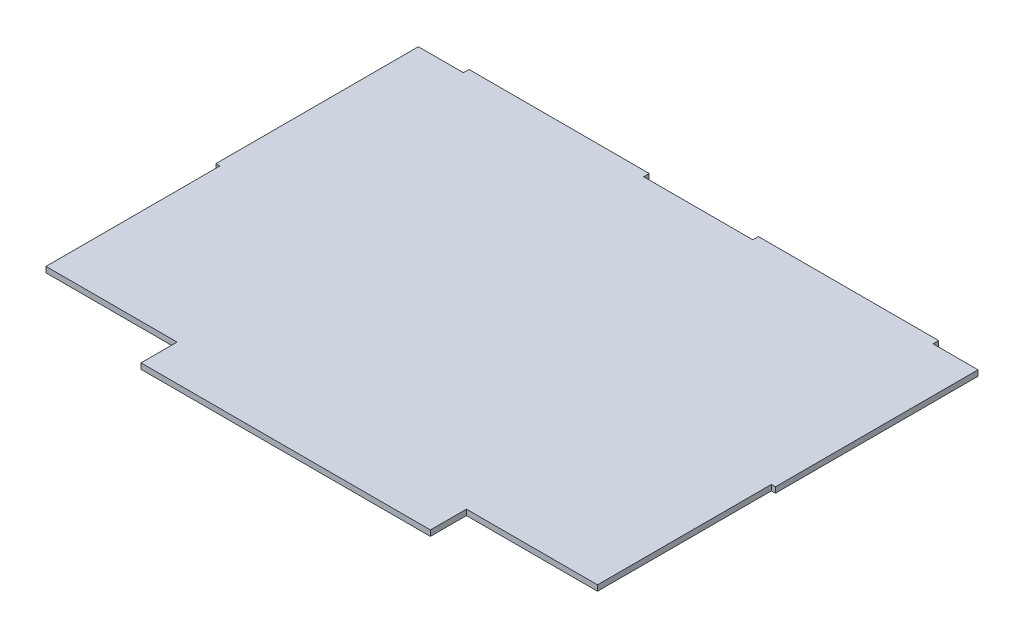
SolidWorks part; units mm, degrees
material "Custom Plastic"
ref_plane "X-Y Datum" through (0, 0, 0) normal (0, 0, 1) x (1, 0, 0)
ref_plane "X-Z Datum" through (0, 0, 0) normal (0, 1, 0) x (1, 0, 0)
ref_plane "Y-Z Datum" through (0, 0, 0) normal (1, 0, 0) x (0, 0, -1)
sketch "Sketch1" plane through (0, 0, 0) normal (0, 0, 1) x (1, 0, 0)
  line L1 (-157.7875, -1.5875) -> (157.7875, -1.5875)
  line L2 (-157.7875, -1.5875) -> (-157.7875, 1.5875)
  line L3 (-157.7875, 1.5875) -> (157.7875, 1.5875)
  line L4 (157.7875, -1.5875) -> (157.7875, 1.5875)
  line L5 (-157.7875, -1.5875) -> (157.7875, 1.5875) construction
  line L6 (-157.7875, 1.5875) -> (157.7875, -1.5875) construction
  point P0 (0, 0)
  dimension "D1" = 315.575
  dimension "D2" = 3.175
extrude "Boss-Extrude1" add sketch "Sketch1" along normal blind 235.775
sketch "Sketch3" plane through (0, 0, 0) normal (0, 0, -1) x (-1, 0, 0)
  line L0 (-157.7875, 0) -> (-81.5875, 0) construction
  line L1 (-157.7875, -1.5875) -> (-157.7875, 1.5875) construction
  line L2 (-157.7875, 1.5875) -> (157.7875, 1.5875) construction
  line L3 (-132.3875, -1.5875) -> (-30.7875, -1.5875)
  line L4 (-132.3875, -1.5875) -> (-132.3875, 1.5875)
  line L5 (-132.3875, 1.5875) -> (-30.7875, 1.5875)
  line L6 (-30.7875, -1.5875) -> (-30.7875, 1.5875)
  line L7 (-132.3875, -1.5875) -> (-30.7875, 1.5875) construction
  line L8 (-132.3875, 1.5875) -> (-30.7875, -1.5875) construction
  line L14 (-157.7875, 1.5875) -> (-132.3875, 1.5875)
  line L15 (-157.7875, 1.5875) -> (-157.7875, -1.5875)
  line L16 (-157.7875, -1.5875) -> (-132.3875, -1.5875)
  line L17 (-132.3875, 1.5875) -> (-132.3875, -1.5875)
  line L19 (-30.7875, 1.5875) -> (-30.7875, -1.5875)
  line L20 (0, 43.0151) -> (0, -43.0151) construction
  line L21 (30.7875, -1.5875) -> (30.7875, 1.5875)
  line L22 (132.3875, -1.5875) -> (132.3875, 1.5875)
  line L23 (132.3875, 1.5875) -> (30.7875, 1.5875)
  line L24 (132.3875, -1.5875) -> (30.7875, 1.5875) construction
  line L25 (132.3875, -1.5875) -> (30.7875, -1.5875)
  line L26 (132.3875, 1.5875) -> (30.7875, -1.5875) construction
  line M2 (-157.7875, 1.5875) -> (-157.7875, -1.5875)
  line M3 (-157.7875, -1.5875) -> (157.7875, -1.5875)
  line M4 (157.7875, -1.5875) -> (157.7875, 1.5875)
  line M5 (157.7875, 1.5875) -> (-157.7875, 1.5875)
  dimension "D1" = 76.2
  dimension "D2" = 101.6
extrude "Cut-Extrude1" cut sketch "Sketch3" against normal blind 3.175 contours L4 M3 M5 M2 | L6 M3 M5 | M3 M4 M5 region at (145.0875, 0, 0) region at (0, 0, 0) region at (-145.0875, 0, 0)
sketch "Sketch5" plane through (0, 1.5875, 0) normal (0, 1, 0) x (1, 0, 0)
  line L1 (-157.7875, -235.775) -> (-155.5015, -235.775)
  line L3 (-157.7875, -235.775) -> (-157.7875, -117.411)
  line L5 (-157.7875, -117.411) -> (-155.5015, -117.411)
  line L6 (-155.5015, -235.775) -> (-155.5015, -117.411)
  line M11 (-157.7875, -3.175) -> (-157.7875, -235.775)
  line M12 (-157.7875, -235.775) -> (157.7875, -235.775)
  dimension "D1" = 118.364
  dimension "D2" = 2.286
extrude "Cut-Extrude2" cut sketch "Sketch5" against normal blind 3.175 and the other way through all contours M12 M11 region at (-156.6445, 1.5875, 176.593)
mirror "Mirror1" about plane through (0, 0, 0) normal (1, 0, 0) of "Cut-Extrude2"
sketch "Sketch6" plane through (0, 1.5875, 0) normal (0, 1, 0) x (1, 0, 0)
  line L0 (-157.7925, -235.775) -> (-157.7925, -134.175) construction
  line L5 (155.5015, -235.775) -> (-155.5015, -235.775) construction
  line L8 (-157.7925, -235.775) -> (-73.389, -235.775)
  line L10 (-157.7925, -215.455) -> (-81.5925, -215.455)
  line L11 (-157.7925, -215.455) -> (-157.7925, -235.775)
  line L12 (-157.7925, -235.775) -> (-81.5925, -235.775)
  line L13 (-81.5925, -215.455) -> (-81.5925, -235.775)
  line M18 (-155.5015, -117.411) -> (-155.5015, -235.775)
  line M19 (-155.5015, -235.775) -> (155.5015, -235.775)
  dimension "D1" = 76.2
  dimension "D2" = 20.32
extrude "Cut-Extrude4" cut sketch "Sketch6" against normal through all contours L13 L10 M18 M19 region at (-118.547, 1.5875, 225.615)
mirror "Mirror2" about plane through (0, 0, 0) normal (1, 0, 0) of "Cut-Extrude4"
